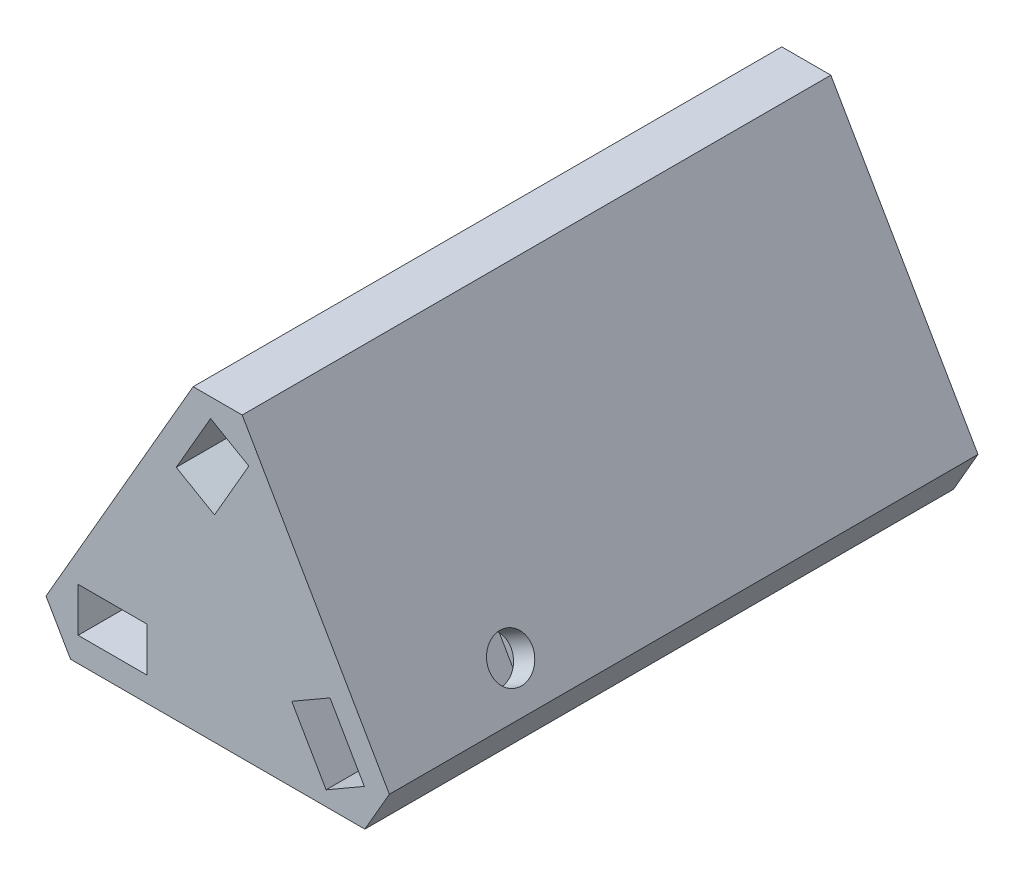
SolidWorks part; units mm, degrees
ref_plane "Front" through (0, 0, 0) normal (0, 0, 1) x (1, 0, 0)
ref_plane "Top" through (0, 0, 0) normal (0, 1, 0) x (1, 0, 0)
ref_plane "Right" through (0, 0, 0) normal (1, 0, 0) x (0, 0, -1)
sketch "Sketch1" plane through (0, 0, 0) normal (0, 0, 1) x (1, 0, 0)
  line L1 (-20, -11.547) -> (20, -11.547)
  line L2 (20, -11.547) -> (0, 23.094)
  line L3 (0, 23.094) -> (-20, -11.547)
  circle A0 centre (0, 0) radius 11.547 construction
  dimension "D1" = 40
extrude "Boss-Extrude1" add sketch "Sketch1" along normal blind 60
chamfer "Chamfer1" distance 5 angle 60 3 edges at (-20, -11.547, 30) (0, 23.094, 30) (20, -11.547, 30) first distance on face at (0, -11.547, 30) first distance on face at (-10, 5.7735, 30)
sketch "Sketch2" plane through (0, 0, 60) normal (0, 0, 1) x (1, 0, 0)
  line L0 (-15, -11.547) -> (15, -11.547) construction
  line L1 (-14.2265, -4.547) -> (-7.2265, -4.547)
  line L2 (-14.2265, -4.547) -> (-14.2265, -9.047)
  line L3 (-14.2265, -9.047) -> (-7.2265, -9.047)
  line L4 (-7.2265, -4.547) -> (-7.2265, -9.047)
  line L5 (-2.5, 18.7639) -> (-17.5, -7.2169) construction
  dimension "D1" = 7
  dimension "D2" = 4.5
  dimension "D3" = 2.5
  dimension "D4" = 1.5
extrude "Cut-Extrude1" cut sketch "Sketch2" against normal blind 19.5
sketch "Sketch3" plane through (0, -11.547, 0) normal (0, -1, 0) x (1, 0, 0)
  line L0 (-10.7265, 40.5) -> (-10.7265, 60) construction
  line L1 (-14.2265, 40.5) -> (-7.2265, 40.5) construction
  line L2 (-15, 60) -> (15, 60) construction
  circle A0 centre (-10.7265, 45.5) radius 2.2
  dimension "D1" = 4.4
  dimension "D2" = 5
extrude "Cut-Extrude2" cut sketch "Sketch3" against normal up to surface (2.5 mm away) up to face at (-10.7265, -9.047, 50.25)
ref_axis "Axis1" through (0, 0, -80.9) along (0, 0, 1)
pattern_circular "CirPattern1" count 3 over 360 about axis through (0, 0, -80.9) along (0, 0, 1) of "Cut-Extrude1", "Cut-Extrude2"
